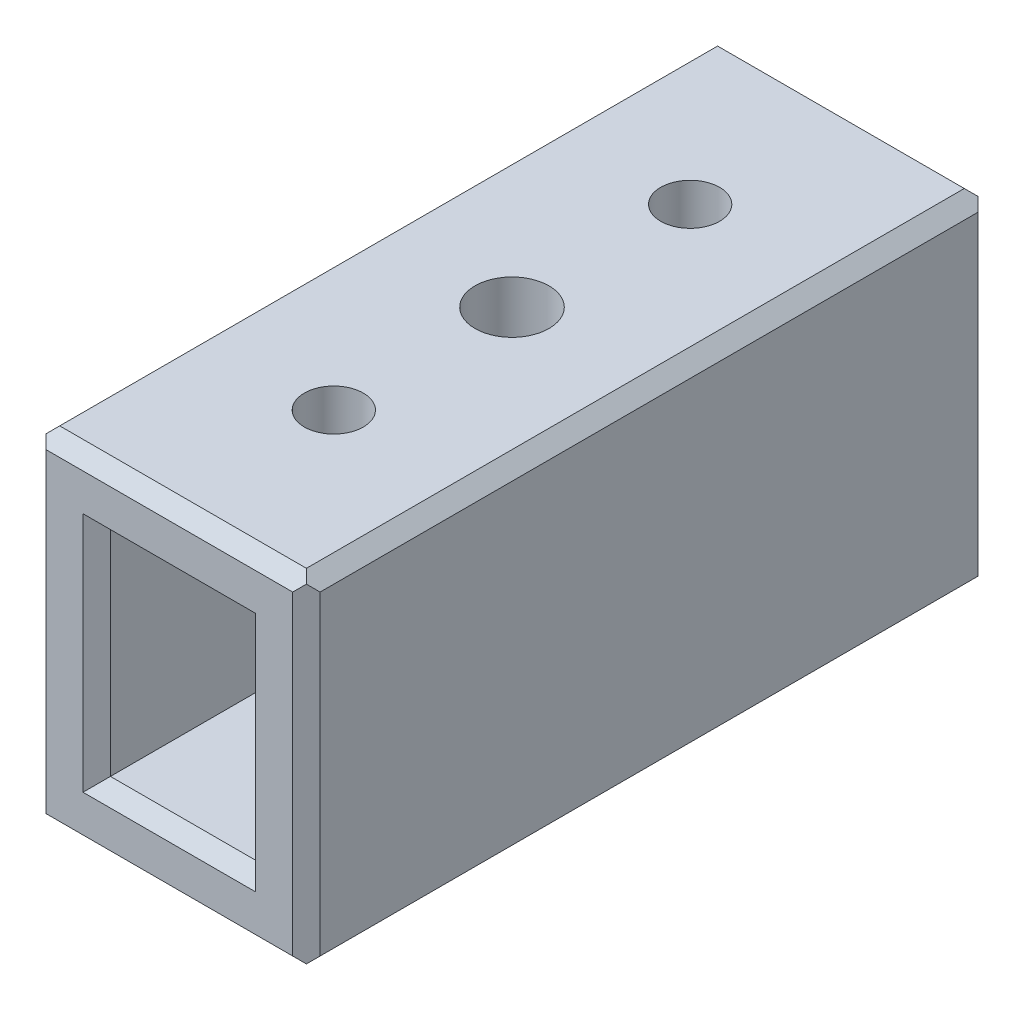
SolidWorks part; units mm, degrees
ref_plane "前视基准面" through (0, 0, 0) normal (0, 0, 1) x (1, 0, 0)
ref_plane "上视基准面" through (0, 0, 0) normal (0, 1, 0) x (1, 0, 0)
ref_plane "右视基准面" through (0, 0, 0) normal (1, 0, 0) x (0, 0, -1)
other "Configuration Table"
sketch "草图2" plane through (0, 0, 0) normal (0, 0, 1) x (1, 0, 0)
  line L0 (-5.3, 7.8) -> (5.3, 7.8)
  line L1 (-5, 7.5) -> (5, 7.5) construction
  line L2 (-5, 7.5) -> (-5, -7.5) construction
  line L3 (-5, -7.5) -> (5, -7.5) construction
  line L4 (5, 7.5) -> (5, -7.5) construction
  line L5 (0, -7.5) -> (0, 7.5) construction
  line L6 (-5, 0) -> (5, 0) construction
  line L7 (5.3, 7.8) -> (5.3, -7.8)
  line L8 (-5.3, -7.8) -> (5.3, -7.8)
  line L9 (-5.3, 7.8) -> (-5.3, -7.8)
  line L11 (-10, 12.5) -> (10, 12.5)
  line L12 (-10, 12.5) -> (-10, -12.5)
  line L13 (-10, -12.5) -> (10, -12.5)
  line L14 (10, 12.5) -> (10, -12.5)
  line L15 (0, -12.5) -> (0, 12.5) construction
  line L16 (-10, 0) -> (10, 0) construction
  point P0 (0, 0)
  point P11 (0, 0)
  dimension "D1" = 15
  dimension "D2" = 10
  dimension "D4" = 25
  dimension "D5" = 20
  dimension "D3" = 0.3
extrude "凸台-拉伸1" add sketch "草图2" against normal blind 50
sketch "草图3" plane through (0, 12.5, 0) normal (0, 1, 0) x (1, 0, 0)
  line L0 (0, 50) -> (0, 0) construction
  line L1 (0, 12) -> (0, 38) construction
  line L4 (-10, 0) -> (10, 0)
  line L5 (10, 0) -> (10, 50)
  line L6 (10, 50) -> (-10, 50)
  line L7 (-10, 50) -> (-10, 0)
  line L8 (-10, 0) -> (10, 0)
  line L9 (10, 0) -> (10, 50)
  line L10 (10, 50) -> (-10, 50)
  line L11 (-10, 50) -> (-10, 0)
  circle A0 centre (0, 38) radius 2.15
  circle A1 centre (0, 12) radius 2.15
  circle A2 centre (0, 25) radius 2.7
  point P10 (0, 25)
  dimension "D2" = 4.3
  dimension "D3" = 4.3
  dimension "D5" = 5.4
  dimension "D4" = 13
  dimension "D1" = 0
extrude "切除-拉伸2" cut sketch "草图3" against normal through all contours A1 | A2 | A0 region at (0, 12.5, -38) region at (0, 12.5, -12) region at (0, 12.5, -25)
chamfer "倒角1" distance 1 angle 45 16 edges at (0, 12.5, -50) (-10, 0, -50) (0, -12.5, -50) (10, 0, -50) (5.3, 0, -50) (0, -7.8, -50) (-5.3, 0, -50) (0, 7.8, -50) (0, -12.5, 0) (-10, 0, 0) (0, 12.5, 0) (10, 0, 0) (0, -7.8, 0) (5.3, 0, 0) (0, 7.8, 0) (-5.3, 0, 0)
chamfer "倒角2" distance 1 angle 45 4 edges at (10, -12.5, -25) (-10, -12.5, -25) (10, 12.5, -25) (-10, 12.5, -25)
